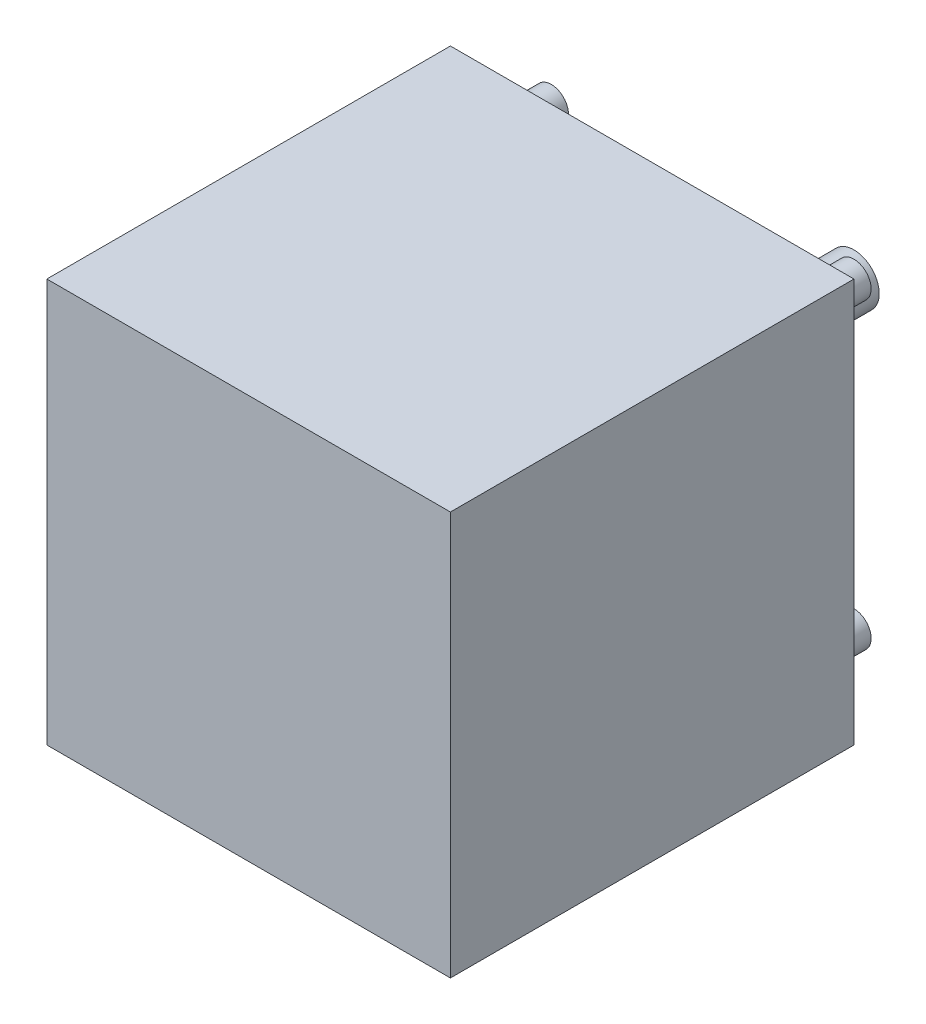
SolidWorks part; units mm, degrees
ref_plane "Front Plane" through (0, 0, 0) normal (0, 0, 1) x (1, 0, 0)
ref_plane "Top Plane" through (0, 0, 0) normal (0, 1, 0) x (1, 0, 0)
ref_plane "Right Plane" through (0, 0, 0) normal (1, 0, 0) x (0, 0, -1)
sketch "Sketch1" plane through (0, 0, 0) normal (0, 0, 1) x (1, 0, 0)
  line L1 (-20, -20) -> (20, -20)
  line L2 (-20, -20) -> (-20, 20)
  line L3 (-20, 20) -> (20, 20)
  line L4 (20, -20) -> (20, 20)
  line L5 (-20, -20) -> (20, 20) construction
  line L6 (-20, 20) -> (20, -20) construction
  point P0 (0, 0)
  dimension "D1" = 40
  dimension "D2" = 40
extrude "Boss-Extrude1" add sketch "Sketch1" along normal blind 40
sketch "Sketch2" plane through (0, 0, 0) normal (0, 0, -1) x (-1, 0, 0)
  line L0 (20, 20) -> (20, -20) construction
  line L2 (20, -20) -> (-20, -20) construction
  circle A0 centre (15, -15) radius 1.7
  dimension "D3" = 3.4
  dimension "D1" = 5
  dimension "D2" = 5
extrude "Boss-Extrude2" add sketch "Sketch2" along normal blind 5
mirror "Mirror1" about plane through (0, 0, 0) normal (1, 0, 0) of "Boss-Extrude2"
mirror "Mirror2" about plane through (0, 0, 0) normal (0, 1, 0) of "Mirror1"
sketch "Sketch3" plane through (0, 0, 0) normal (0, 0, -1) x (-1, 0, 0)
  circle A0 centre (0, 0) radius 2.5
  dimension "D1" = 5
extrude "Boss-Extrude3" add sketch "Sketch3" along normal blind 20
equation "\"D1@Boss-Extrude2\" = \"mat@V1.assembly\""
